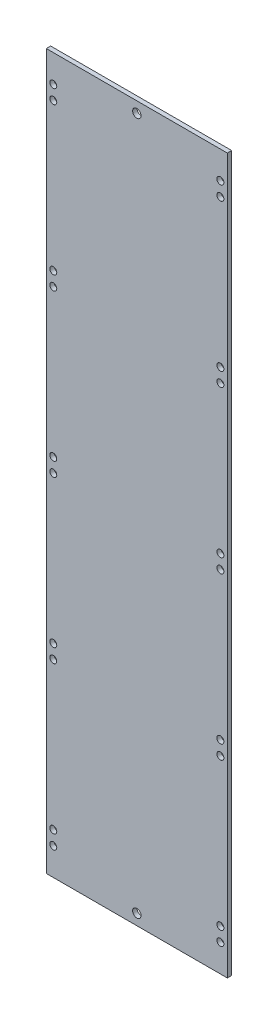
SolidWorks part; units mm, degrees
ref_plane "Front Plane" through (0, 0, 0) normal (0, 0, 1) x (1, 0, 0)
ref_plane "Top Plane" through (0, 0, 0) normal (0, 1, 0) x (1, 0, 0)
ref_plane "Right Plane" through (0, 0, 0) normal (1, 0, 0) x (0, 0, -1)
sketch "Sketch1" plane through (0, 0, 0) normal (0, 0, 1) x (1, 0, 0)
  line L1 (0, 0) -> (83, 0)
  line L2 (0, 0) -> (0, 327.5)
  line L3 (0, 327.5) -> (83, 327.5)
  line L4 (83, 0) -> (83, 327.5)
  dimension "D1" = 83
  dimension "D2" = 327.5
extrude "Boss-Extrude1" add sketch "Sketch1" along normal blind 2
sketch "Sketch2" plane through (0, 0, 2) normal (0, 0, 1) x (1, 0, 0)
  line L0 (0, 327.5) -> (0, 0) construction
  line L1 (83, 327.5) -> (0, 327.5) construction
  line L2 (0, 0) -> (83, 0) construction
  circle A0 centre (3.2, 314.9) radius 1.6
  circle A1 centre (3.2, 308.5) radius 1.6
  circle A2 centre (79.8, 314.9) radius 1.6
  circle A3 centre (79.8, 308.5) radius 1.6
  circle A4 centre (3.2, 240.925) radius 1.6
  circle A5 centre (3.2, 234.525) radius 1.6
  circle A6 centre (79.8, 240.925) radius 1.6
  circle A7 centre (79.8, 234.525) radius 1.6
  circle A8 centre (3.2, 166.95) radius 1.6
  circle A9 centre (3.2, 160.55) radius 1.6
  circle A10 centre (79.8, 166.95) radius 1.6
  circle A11 centre (79.8, 160.55) radius 1.6
  circle A12 centre (3.2, 92.975) radius 1.6
  circle A13 centre (3.2, 86.575) radius 1.6
  circle A14 centre (79.8, 92.975) radius 1.6
  circle A15 centre (79.8, 86.575) radius 1.6
  circle A16 centre (3.2, 19) radius 1.6
  circle A17 centre (3.2, 12.6) radius 1.6
  circle A18 centre (79.8, 19) radius 1.6
  circle A19 centre (79.8, 12.6) radius 1.6
  dimension "D1" = 3.2
  dimension "D4" = 3.2
  dimension "D2" = 3.2
  dimension "D3" = 12.6
  dimension "D5" = 6.4
  dimension "D6" = 3.2
  dimension "D9" = 12.6
  dimension "D7" = 2
  dimension "D8" = 5
extrude "Cut-Extrude1" cut sketch "Sketch2" against normal blind 2
sketch "Sketch3" plane through (0, 0, 2) normal (0, 0, 1) x (1, 0, 0)
  line L0 (83, 327.5) -> (0, 327.5) construction
  line L1 (0, 327.5) -> (0, 0) construction
  line L2 (83, 0) -> (83, 327.5) construction
  line L3 (0, 0) -> (83, 0) construction
  circle A0 centre (41.5, 322.524) radius 1.93
  circle A1 centre (41.5, 4.976) radius 1.93
  dimension "D1" = 3.86
  dimension "D5" = 3.86
  dimension "D2" = 4.976
  dimension "D3" = 41.5
  dimension "D4" = 41.5
  dimension "D6" = 41.5
  dimension "D7" = 41.5
  dimension "D8" = 4.976
extrude "Cut-Extrude2" cut sketch "Sketch3" against normal blind 2
